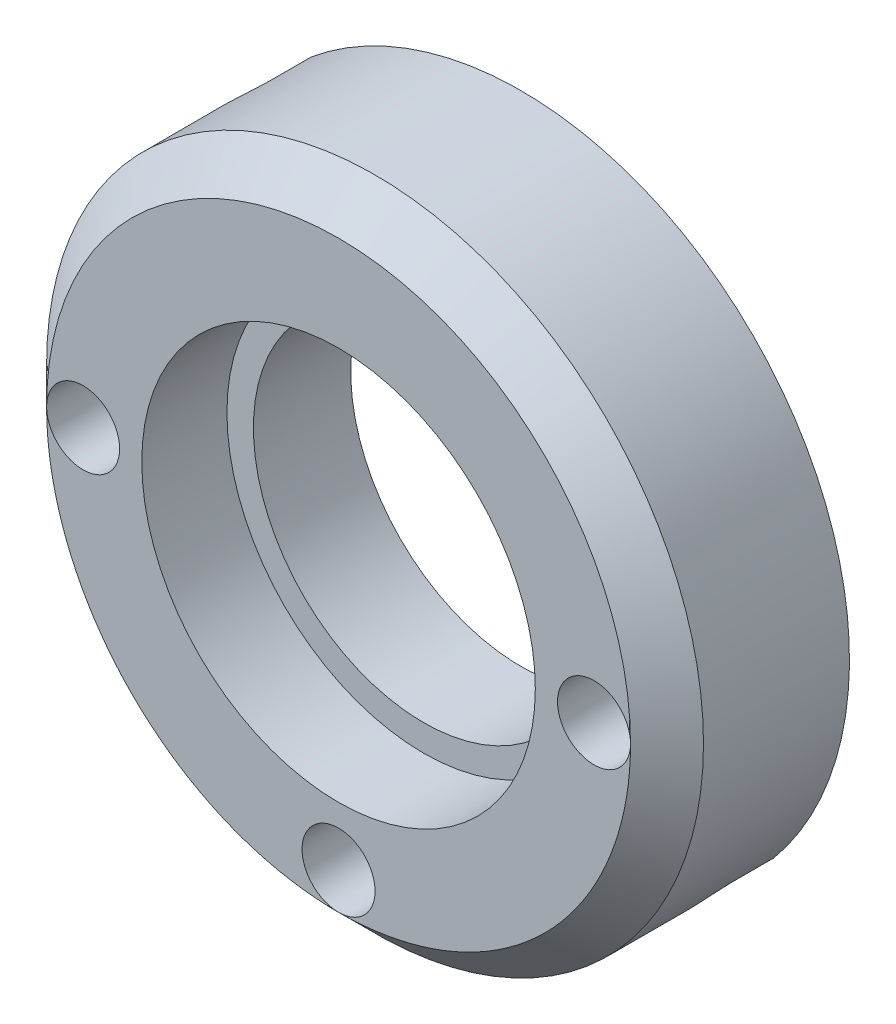
SolidWorks part; units mm, degrees
ref_plane "Спереди" through (0, 0, 0) normal (0, 0, 1) x (1, 0, 0)
ref_plane "Сверху" through (0, 0, 0) normal (0, 1, 0) x (1, 0, 0)
ref_plane "Справа" through (0, 0, 0) normal (1, 0, 0) x (0, 0, -1)
sketch "Эскиз1" plane through (0, 0, 0) normal (0, 0, 1) x (1, 0, 0)
  circle A0 centre (0, 0) radius 27
  dimension "D1" = 54
extrude "тело" add sketch "Эскиз1" along normal blind 15
sketch "Эскиз2" plane through (0, 0, 15) normal (0, 0, 1) x (1, 0, 0)
  circle A0 centre (0, 0) radius 16.175
  dimension "D1" = 32.35
extrude "углубление под подшипник" cut sketch "Эскиз2" against normal blind 7
sketch "Эскиз3" plane through (0, 0, 8) normal (0, 0, 1) x (1, 0, 0)
  circle A0 centre (0, 0) radius 14
  dimension "D1" = 28
extrude "сквозное отверстие" cut sketch "Эскиз3" against normal through all
sketch "Эскиз5" plane through (0, 0, 15) normal (0, 0, 1) x (1, 0, 0)
  circle A0 centre (0, 0) radius 21 construction
  circle A1 centre (-21, 0) radius 1.65
  circle A3 centre (21, 0) radius 1.65
  circle A4 centre (0, -21) radius 1.65
  point P2 (0, 0)
  point P3 (0, 0)
  point P10 (0, 0)
  point P11 (21.83, 4.2938)
  point P12 (23.9, 0)
  point P13 (-23.9, 0)
  point P14 (0, -23.9)
  dimension "D1" = 42
  dimension "D2" = 3.3
extrude "крепежные отверстия" cut sketch "Эскиз5" against normal through all
sketch "Эскиз6" plane through (0, 0, 15) normal (0, 0, 1) x (1, 0, 0)
  circle A0 centre (-21, 0) radius 3
  circle A2 centre (21, 0) radius 3
  circle A3 centre (0, -21) radius 3
  dimension "D1" = 6
extrude "отверстия под шляпки" cut sketch "Эскиз6" against normal blind 5
chamfer "Фаска1" distance 1.5 angle 45 3 edges at (1.65, -21, 10) (22.65, 0, 10) (-19.35, 0, 10)
chamfer "Фаска2" distance 3 angle 45 1 edges at (27, 0, 15)
sketch3d "Трехмерный эскиз1"
  line L0 (0, 0, 0) -> (-21.4087, 21.4087, 0) construction
  point P0 (0, 0, 0)
  point P3 (0, 0, 0)
sketch "Эскиз7" plane through (0, 0, 0) normal (0.7071, -0.7071, 0) x (0, 0, -1)
  line L0 (0, 2.5) -> (-3, 2.5)
  line L1 (0, 2.5) -> (0, -2.5)
  line L2 (0, -2.5) -> (-3, -2.5)
  arc A0 (-3, 2.5) -> (-3, -2.5) centre (-3, 0) ccw
  point P2 (0, 0)
  dimension "D1" = 2.5
  dimension "D2" = 3
extrude "Вырез-Вытянуть1" cut sketch "Эскиз7" against normal through all and the other way through all
